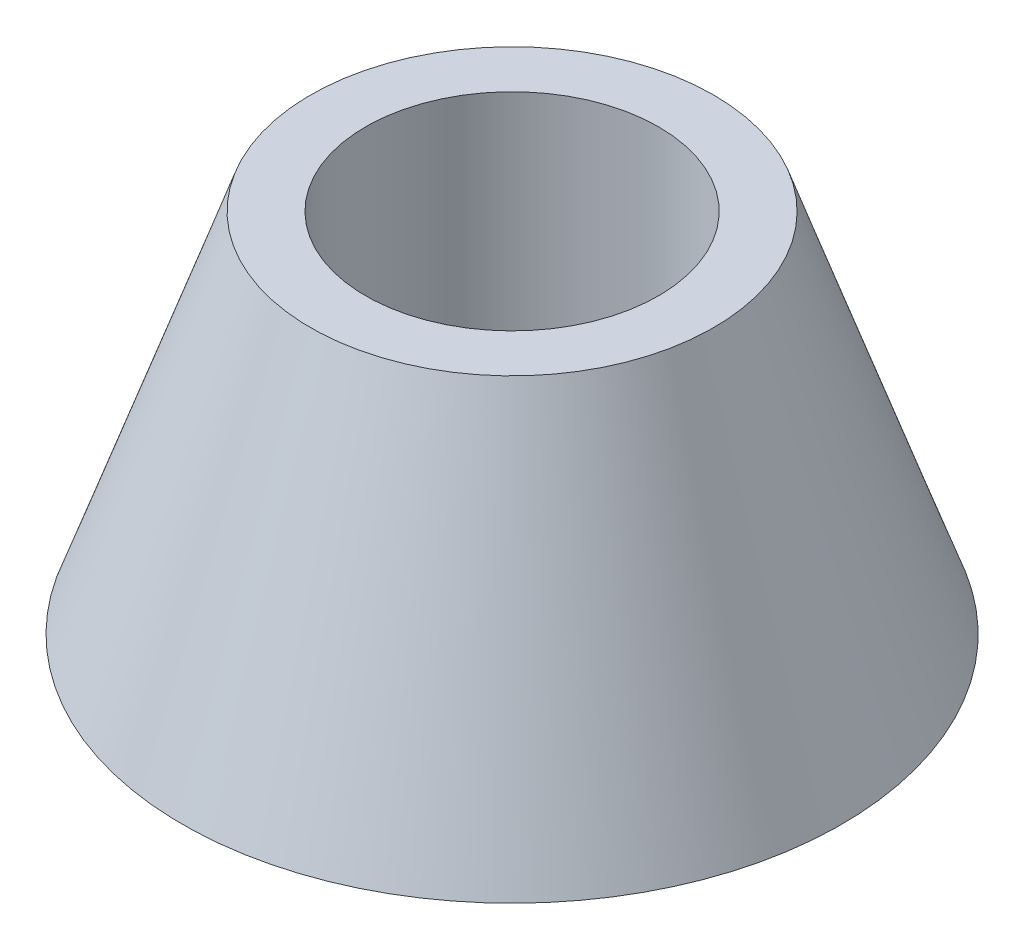
SolidWorks part; units mm, degrees
ref_plane "Front Plane" through (0, 0, 0) normal (0, 0, 1) x (1, 0, 0)
ref_plane "Top Plane" through (0, 0, 0) normal (0, 1, 0) x (1, 0, 0)
ref_plane "Right Plane" through (0, 0, 0) normal (1, 0, 0) x (0, 0, -1)
sketch "Sketch1" plane through (0, 0, 0) normal (0, 0, 1) x (1, 0, 0)
  line L0 (-4.3688, 7.9375) -> (-7.1437, 0)
  line L3 (-7.1437, 0) -> (-3.175, 0)
  line L4 (0, 0) -> (0, 7.9375) construction
  line L7 (-4.3688, 7.9375) -> (-3.175, 7.9375)
  line L8 (-3.175, 7.9375) -> (-3.175, 0)
  point P1 (-3.175, 7.9375)
revolve "Revolve1" add sketch "Sketch1" angle 360 about L4
sketch "Sketch2" plane through (0, 0, 0) normal (1, 0, 0) x (0, 0, -1)
  line L0 (-3.175, 0) -> (3.175, 0) construction
  line L1 (-3.175, 0) -> (-3.175, 7.9375) construction
  line L2 (3.175, 0) -> (3.175, 7.9375) construction
  point P2 (0, 0)
  dimension "D1" = 6.35
  dimension "D2" = 7.9375
ref_axis "Center Axis 1" through (0, 7.9375, 0) along (0, -1, 0)
ref_plane "Contact Plane 1" through (0, 7.9375, 0) normal (0, 1, 0) x (1, 0, 0)
ref_plane "Contact Plane 2" through (0, 0, 0) normal (0, -1, 0) x (-1, 0, 0)
equation "\"D1@Sketch2\"=\"ID@sketch1\""
equation "\"D2@Sketch2\"=\"OAH@sketch1\""
